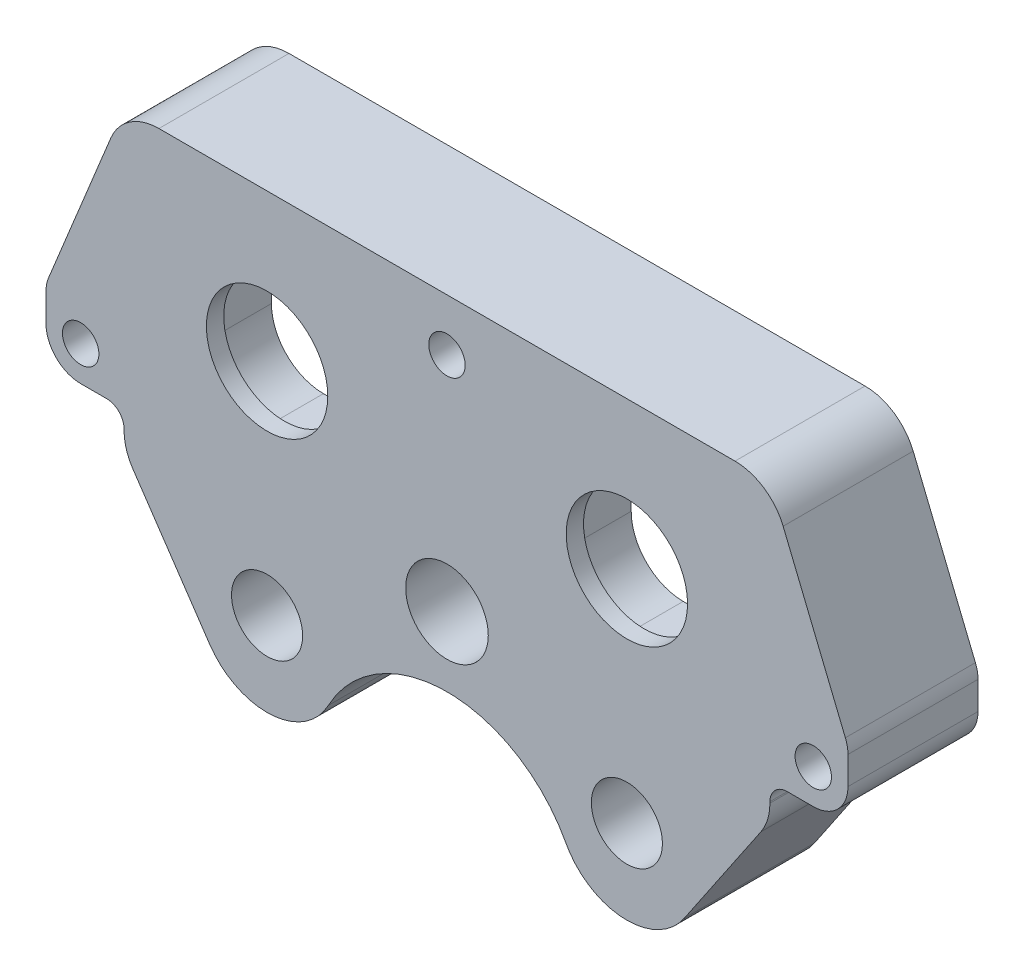
SolidWorks part; units mm, degrees
ref_plane "Front Plane" through (0, 0, 0) normal (0, 0, 1) x (1, 0, 0)
ref_plane "Top Plane" through (0, 0, 0) normal (0, 1, 0) x (1, 0, 0)
ref_plane "Right Plane" through (0, 0, 0) normal (1, 0, 0) x (0, 0, -1)
sketch "Sketch1" plane through (0, 0, 0) normal (0, 0, 1) x (1, 0, 0)
  line L0 (56, 15) -> (27, 15)
  line L1 (14.5, 15) -> (-14.5, 15)
  line L2 (14.5, 15) -> (14.5, -15)
  line L3 (14.5, -15) -> (-14.5, -15)
  line L4 (-14.5, 15) -> (-14.5, -15)
  line L5 (14.5, 15) -> (-14.5, -15) construction
  line L6 (14.5, -15) -> (-14.5, 15) construction
  line L7 (-16.75, -42) -> (16.75, -42)
  line L8 (-16.75, -42) -> (-16.75, 16)
  line L9 (-16.75, 16) -> (16.75, 16)
  line L10 (16.75, -42) -> (16.75, 16)
  line L11 (56, 15) -> (56, -15)
  line L12 (56, -15) -> (27, -15)
  line L13 (27, 15) -> (27, -15)
  line L14 (56, 15) -> (27, -15) construction
  line L15 (56, -15) -> (27, 15) construction
  line L16 (24.75, -42) -> (58.25, -42)
  line L17 (24.75, -42) -> (24.75, 16)
  line L18 (24.75, 16) -> (58.25, 16)
  line L19 (58.25, -42) -> (58.25, 16)
  circle A0 centre (0, 0) radius 19.05 construction
  circle A1 centre (41.5, 0) radius 19.05 construction
  circle A2 centre (20.75, -14.6491) radius 6.35 construction
  circle A3 centre (20.75, -14.6491) radius 41.275 construction
  circle A4 centre (0, 0) radius 7
  circle A5 centre (41.5, 0) radius 7
  circle A6 centre (0, -25.4) radius 4.3
  circle A7 centre (0, -27.1) radius 6.75
  circle A8 centre (41.5, -27.1) radius 6.75
  circle A9 centre (41.5, -25.4) radius 4.3
  point P0 (0, 0)
  point P10 (41.5, 0)
  point P11 (0, -42)
  point P22 (41.5, -42)
  dimension "D6" = 38.1
  dimension "D12" = 38.1
  dimension "D13" = 12.7
  dimension "D15" = 82.55
  dimension "D20" = 14
  dimension "D21" = 14
  dimension "D16" = 8.6
  dimension "D18" = 13.5
  dimension "D1" = 33.5
  dimension "D2" = 29
  dimension "D3" = 30
  dimension "D4" = 16
  dimension "D5" = 58
  dimension "D7" = 33.5
  dimension "D8" = 29
  dimension "D9" = 30
  dimension "D10" = 16
  dimension "D11" = 58
  dimension "D14" = 8
  dimension "D17" = 10.4
  dimension "D19" = 1.7
sketch "Sketch5" plane through (0, 0, 0) normal (0, 0, 1) x (1, 0, 0)
  line L0 (56, 15) -> (27, -15) construction
  line L1 (14.5, 15) -> (-14.5, 15) construction
  line L2 (-16.5, 17) -> (58, 17)
  line L3 (-16.5, 17) -> (-16.5, -35.1)
  line L4 (-16.5, -35.1) -> (58, -35.1)
  line L5 (58, 17) -> (58, -35.1)
  line L6 (-14.5, 15) -> (-14.5, -15) construction
  line L7 (56, 15) -> (56, -15) construction
  line L8 (14.5, -15) -> (-14.5, -15) construction
  line L9 (-16.5, -17) -> (-6.6243, -31.5853)
  line L10 (56, -15) -> (27, -15) construction
  line L11 (58, -17) -> (48.1243, -31.5853)
  line L12 (-25.5, -5) -> (-16.5, 17)
  line L13 (-16.5, -5) -> (-25.5, -5)
  line L14 (-16.5, -5) -> (-16.5, -13)
  line L15 (-16.5, -13) -> (-25.5, -13)
  line L16 (-25.5, -5) -> (-25.5, -13)
  line L17 (58, -5) -> (67, -5)
  line L18 (58, -5) -> (58, -13)
  line L19 (58, -13) -> (67, -13)
  line L20 (67, -5) -> (67, -13)
  line L21 (58, 17) -> (67, -5)
  circle A0 centre (0, 0) radius 7
  circle A1 centre (41.5, 0) radius 7
  circle A2 centre (20.75, -14.6491) radius 4.7625
  circle A3 centre (0, -25.4) radius 4.1
  circle A4 centre (41.5, -25.4) radius 4.1
  circle A5 centre (41.5, -27.1) radius 6.75
  circle A6 centre (0, -27.1) radius 6.75
  circle A7 centre (0, -27.1) radius 8
  circle A8 centre (41.5, -27.1) radius 8
  circle A9 centre (-21.5, -9) radius 2.1
  circle A10 centre (20.75, 11) radius 2.1
  circle A11 centre (63, -9) radius 2.1
  circle A12 centre (20.75, -38.1651) radius 15.5159
  point P32 (-16.5, -17)
  point P39 (58, -17)
  point P58 (20.75, -22.6491)
  dimension "D1" = 9.525
  dimension "D2" = 14
  dimension "D3" = 14
  dimension "D4" = 8.2
  dimension "D5" = 8
  dimension "D6" = 13.5
  dimension "D7" = 13.5
  dimension "D18" = 4.2
  dimension "D22" = 4.2
  dimension "D26" = 4.2
  dimension "D8" = 8
  dimension "D9" = 2
  dimension "D10" = 2
  dimension "D11" = 2
  dimension "D12" = 2
  dimension "D13" = 2
  dimension "D14" = 8
  dimension "D15" = 9
  dimension "D16" = 9
  dimension "D17" = 9
  dimension "D19" = 8
  dimension "D20" = 5
  dimension "D21" = 4
  dimension "D23" = 20
  dimension "D24" = 4
  dimension "D25" = 5
extrude "Boss-Extrude5" add sketch "Sketch5" against normal blind 15 contours A8 A5 | A7 A6 | A6 A3 | A5 A4 | A8 L11 L5 L2 L3 L9 A7 L4 A10 A2 A1 A0 | L13 L16 L15 L3 A9 | L20 L17 L5 L19 A11 | L13 L3 L12 | L21 L5 L17 region at (20.75, -3.0746, 0) region at (-19.5, 2.3333, 0) region at (61, 2.3333, 0) region at (-16.6204, -9, 0) region at (62.5, -5.1204, 0) region at (-2.2794, -19.668, 0) region at (45.1434, -33.967, 0) region at (34.9409, -27.1, 0) region at (-6.5591, -27.1, 0)
extrude "Cut-Extrude1" cut sketch "Sketch1" along normal blind 13 from surface contours L1 L4 L3 L2 A4 | L0 L13 L12 L11 A5 region at (55.5827, 0, 0) region at (14.0827, 0, 0) starting at face at (20.75, -13.3152, -15)
extrude "Cut-Extrude2" cut sketch "Sketch5<3>" along normal blind 2 from surface contours A5 A4 | A6 A3 region at (34.9409, -27.1, 0) region at (-6.5591, -27.1, 0) starting at face at (0, 0, -15)
sketch "Sketch5<3>" plane through (0, 0, 0) normal (0, 0, 1) x (1, 0, 0) same geometry as "Sketch5"
fillet "Fillet1" radius 6 8 edges at (56, 15, -8.5) (56, -15, -8.5) (27, -15, -8.5) (27, 15, -8.5) (14.5, -15, -8.5) (-14.5, -15, -8.5) (-14.5, 15, -8.5) (14.5, 15, -8.5)
fillet "Fillet2" radius 4 4 edges at (-25.5, -5, -7.5) (-25.5, -13, -7.5) (67, -5, -7.5) (67, -13, -7.5)
fillet "Fillet3" radius 6 4 edges at (-16.5, -17, -7.5) (58, -17, -7.5) (-16.5, 17, -7.5) (58, 17, -7.5)
fillet "Fillet4" radius 2 2 edges at (-16.5, -13, -7.5) (58, -13, -7.5)
extrude "Boss-Extrude6" add sketch "Sketch5<4>" along normal blind 2.3 from surface contours A2 region at (20.75, -14.6491, 0) starting at face at (6.75, -27.1, -15)
sketch "Sketch5<4>" plane through (0, 0, 0) normal (0, 0, 1) x (1, 0, 0) same geometry as "Sketch5"
sketch "Sketch6" plane through (0, 0, 0) normal (0, 0, 1) x (1, 0, 0)
  line L1 (-17.8338, -9) -> (-19.6669, -5.825)
  line L2 (-19.6669, -5.825) -> (-23.3331, -5.825)
  line L3 (-23.3331, -5.825) -> (-25.1662, -9)
  line L4 (-25.1662, -9) -> (-23.3331, -12.175)
  line L5 (-23.3331, -12.175) -> (-19.6669, -12.175)
  line L6 (-19.6669, -12.175) -> (-17.8338, -9)
  line L7 (24.4162, 11) -> (22.5831, 14.175)
  line L8 (22.5831, 14.175) -> (18.9169, 14.175)
  line L9 (18.9169, 14.175) -> (17.0838, 11)
  line L10 (17.0838, 11) -> (18.9169, 7.825)
  line L11 (18.9169, 7.825) -> (22.5831, 7.825)
  line L12 (22.5831, 7.825) -> (24.4162, 11)
  line L13 (59.3338, -9) -> (61.1669, -12.175)
  line L14 (61.1669, -12.175) -> (64.8331, -12.175)
  line L15 (64.8331, -12.175) -> (66.6662, -9)
  line L16 (66.6662, -9) -> (64.8331, -5.825)
  line L17 (64.8331, -5.825) -> (61.1669, -5.825)
  line L18 (61.1669, -5.825) -> (59.3338, -9)
  circle A0 centre (-21.5, -9) radius 3.175 construction
  circle A1 centre (20.75, 11) radius 3.175 construction
  circle A2 centre (63, -9) radius 3.175 construction
  dimension "D1" = 6.35
  dimension "D2" = 6.35
  dimension "D3" = 6.35
